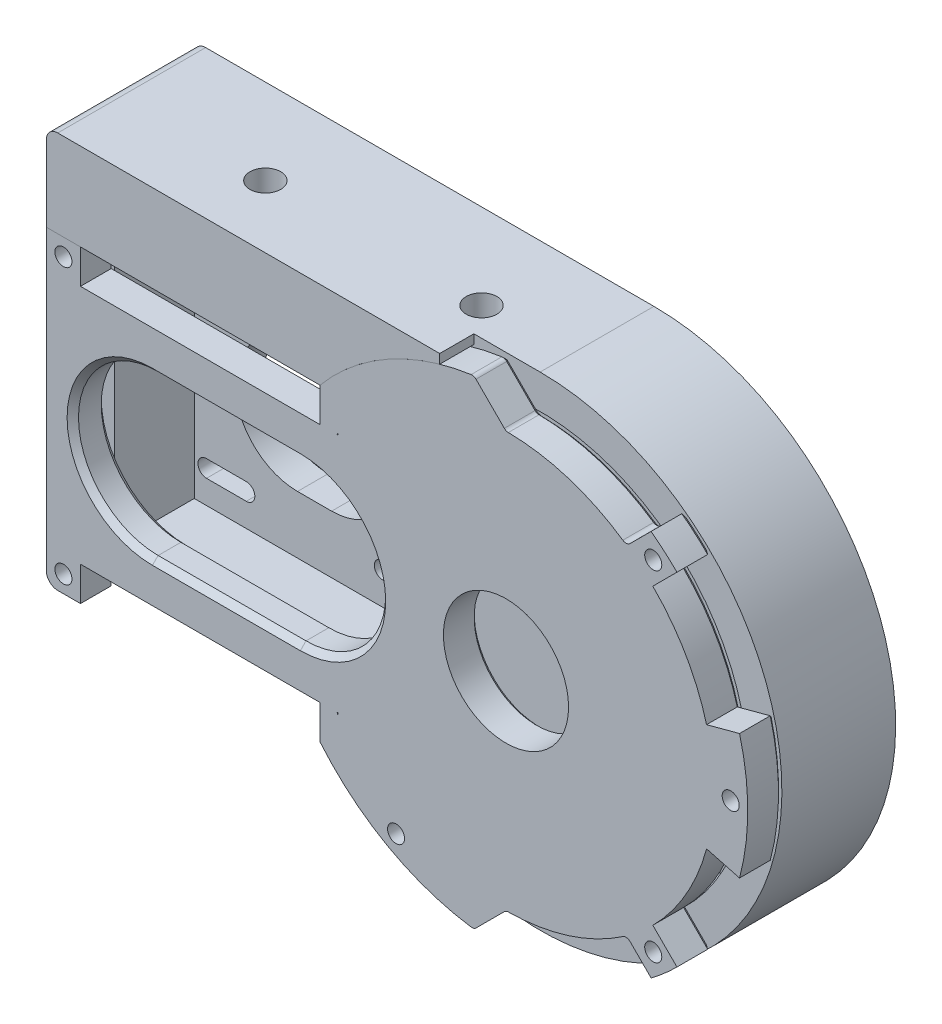
SolidWorks part; units mm, degrees
note: The reader was unsure of these and kept them because the rebuilt part matched: shared geometry of "Sketch3<3>", "Sketch1<3>".
other "Vista explosionada1" [suppressed]
other "Paso de explosión1" [suppressed]
other "Línea de explosión1"
other "Paso de explosión2" [suppressed]
other "Línea de explosión1"
ref_plane "Front Plane" through (0, 0, 0) normal (0, 0, 1) x (1, 0, 0)
ref_plane "Top Plane" through (0, 0, 0) normal (0, 1, 0) x (1, 0, 0)
ref_plane "Right Plane" through (0, 0, 0) normal (1, 0, 0) x (0, 0, -1)
sketch "Sketch1" plane through (0, 0, 0) normal (0, 0, 1) x (1, 0, 0)
  line L0 (21.15, 27.15) -> (-27.15, 27.15)
  line L1 (21.15, -21.15) -> (-21.15, -21.15)
  line L2 (21.15, -21.15) -> (21.15, 21.15)
  line L3 (21.15, 21.15) -> (-21.15, 21.15)
  line L4 (-21.15, -21.15) -> (-21.15, 21.15)
  line L5 (21.15, -21.15) -> (-21.15, 21.15) construction
  line L6 (21.15, 21.15) -> (-21.15, -21.15) construction
  line L7 (21.15, 21.15) -> (71.15, 21.15)
  line L8 (21.15, 21.15) -> (21.15, -21.15)
  line L9 (21.15, -21.15) -> (71.15, -21.15)
  line L10 (71.15, 21.15) -> (71.15, -21.15)
  line L11 (-27.15, -27.15) -> (-27.15, 27.15)
  line L12 (21.15, -27.15) -> (-27.15, -27.15)
  line L13 (21.15, 27.15) -> (24.15, 27.15)
  line L14 (24.15, 27.15) -> (24.15, 21.15)
  line L15 (21.15, -27.15) -> (24.15, -27.15)
  line L16 (24.15, -27.15) -> (24.15, -21.15)
  line L17 (21.15, 33.15) -> (-33.15, 33.15)
  line L18 (-33.15, -33.15) -> (-33.15, 33.15)
  line L19 (21.15, -33.15) -> (-33.15, -33.15)
  circle A0 centre (-15.5, 15.5) radius 1.5
  circle A1 centre (15.5, 15.5) radius 1.5
  circle A2 centre (15.5, -15.5) radius 1.5
  circle A3 centre (-15.5, -15.5) radius 1.5
  circle A4 centre (0, 0) radius 11
  circle A5 centre (0, 0) radius 2.5
  circle A6 centre (53.65, 0) radius 11
  point P0 (0, 0)
  dimension "D2" = 3
  dimension "D3" = 22
  dimension "D4" = 5
  dimension "D6" = 22
  dimension "D1" = 42.3
  dimension "D5" = 31
  dimension "D7" = 53.65
  dimension "D8" = 50
  dimension "D10" = 3
  dimension "D9" = 6
  dimension "D11" = 12
extrude "Boss-Extrude1" add sketch "Sketch1" along normal blind 6 contours L4 L1 L2 L3 A4 A3 A2 A1 A0 | L10 L7 L2 L9 A6
sketch "Sketch3" plane through (0, 0, 0) normal (0, 0, 1) x (1, 0, 0)
  line L0 (16.7864, 21.15) -> (23.9023, 21.15)
  line L1 (71.15, 21.15) -> (-21.15, 21.15) construction
  line L2 (16.7864, -21.15) -> (23.9023, -21.15)
  line L3 (71.15, -21.15) -> (-21.15, -21.15) construction
  circle A1 centre (53.65, 0) radius 36.5
  circle A2 centre (53.65, 0) radius 42.5
  circle A3 centre (53.65, 0) radius 11
  dimension "D1" = 73
  dimension "D3" = 22
  dimension "D2" = 6
extrude "Boss-Extrude2" add sketch "Sketch3" along normal up to surface (6 mm away) contours A1
extrude "Boss-Extrude3" add sketch "Sketch3<3>" along normal blind 20 contours L2 A2 L0 A1
sketch "Sketch3<3>" plane through (0, 0, 0) normal (0, 0, 1) x (1, 0, 0) same geometry as "Sketch3"
extrude "Boss-Extrude4" add sketch "Sketch1<3>" along normal up to surface (20 mm away) contours L15 L16 L9 L1 L4 L3 L7 L14 L13 L0 L11 L12 up to face at (56.7472, 0, 20)
sketch "Sketch1<3>" plane through (0, 0, 0) normal (0, 0, 1) x (1, 0, 0) same geometry as "Sketch1"
sketch "Sketch4" plane through (0, 0, 6) normal (0, 0, 1) x (1, 0, 0)
  line L0 (-19, 15.5) -> (-12, 15.5) construction
  line L1 (-19, 17) -> (-12, 17)
  line L2 (-19, 14) -> (-12, 14)
  line L3 (12, 15.5) -> (19, 15.5) construction
  line L4 (12, 17) -> (19, 17)
  line L5 (12, 14) -> (19, 14)
  line L6 (12, -15.5) -> (19, -15.5) construction
  line L7 (12, -14) -> (19, -14)
  line L8 (12, -17) -> (19, -17)
  line L9 (-12, -15.5) -> (-19, -15.5) construction
  line L10 (-12, -17) -> (-19, -17)
  line L11 (-12, -14) -> (-19, -14)
  line L12 (-3, 0) -> (3, 0) construction
  line L13 (-3, 11) -> (3, 11)
  line L14 (-3, -11) -> (3, -11)
  arc A0 (-19, 17) -> (-19, 14) centre (-19, 15.5) ccw
  arc A1 (-12, 14) -> (-12, 17) centre (-12, 15.5) ccw
  arc A2 (12, 17) -> (12, 14) centre (12, 15.5) ccw
  arc A3 (19, 14) -> (19, 17) centre (19, 15.5) ccw
  arc A4 (12, -14) -> (12, -17) centre (12, -15.5) ccw
  arc A5 (19, -17) -> (19, -14) centre (19, -15.5) ccw
  arc A6 (-12, -17) -> (-12, -14) centre (-12, -15.5) ccw
  arc A7 (-19, -14) -> (-19, -17) centre (-19, -15.5) ccw
  circle A8 centre (-15.5, -15.5) radius 1.5 construction
  circle A9 centre (-15.5, 15.5) radius 1.5 construction
  circle A10 centre (15.5, 15.5) radius 1.5 construction
  circle A11 centre (15.5, -15.5) radius 1.5 construction
  arc A12 (-3, 11) -> (-3, -11) centre (-3, 0) ccw
  arc A13 (3, -11) -> (3, 11) centre (3, 0) ccw
  point P2 (-15.5, 15.5)
  point P7 (15.5, 15.5)
  point P14 (15.5, -15.5)
  point P21 (-15.5, -15.5)
  point P28 (0, 0)
  dimension "D2" = 1.5
  dimension "D4" = 28
  dimension "D1" = 7
  dimension "D3" = 22
extrude "Cut-Extrude1" cut sketch "Sketch4" against normal through all
sketch "Sketch5" plane through (0, 0, 20) normal (0, 0, 1) x (1, 0, 0)
  line L0 (-27.15, -27.15) -> (20.9525, -27.15) construction
  line L1 (-27.15, -27.15) -> (-27.15, 27.15) construction
  line L2 (-27.15, 27.15) -> (20.9525, 27.15) construction
  line L3 (-27.15, -27.15) -> (20.9525, -27.15)
  line L4 (-27.15, -27.15) -> (-27.15, 27.15)
  line L5 (-27.15, 27.15) -> (20.9525, 27.15)
  line L6 (-21.15, -21.15) -> (-21.15, 21.15) construction
  line L8 (-21.15, -21.15) -> (24.15, -21.15) construction
  line L9 (-21.15, -21.15) -> (-21.15, 21.15)
  line L10 (23.9023, -21.15) -> (-21.15, -21.15)
  line L11 (-21.15, 21.15) -> (23.9023, 21.15)
  line L12 (53.65, 0) -> (83.702, 30.052)
  line L13 (-21.15, -21.15) -> (20.9525, -21.15)
  line L14 (-21.15, -21.15) -> (-21.15, -27.15)
  line L15 (-21.15, -27.15) -> (20.9525, -27.15)
  line L16 (20.9525, -21.15) -> (20.9525, -27.15)
  line L17 (-21.15, 21.15) -> (20.9525, 21.15)
  line L18 (-21.15, 21.15) -> (-21.15, 27.15)
  line L19 (-21.15, 27.15) -> (20.9525, 27.15)
  line L20 (20.9525, 21.15) -> (20.9525, 27.15)
  line L21 (53.65, 0) -> (83.702, -30.052)
  line L22 (53.65, 0) -> (116.9274, 0) construction
  line L23 (45.1647, 0) -> (79.4594, -34.2947)
  line L24 (45.1647, 0) -> (79.4594, 34.2947)
  line L25 (53.65, 42.5) -> (53.65, -42.5)
  line L26 (53.65, 0) -> (94.7018, 10.9998)
  line L27 (53.65, 0) -> (94.7018, -10.9998)
  line L28 (24.15, 21.15) -> (-21.15, 21.15) construction
  arc A0 (20.9525, -27.15) -> (20.9525, 27.15) centre (53.65, 0) ccw construction
  arc A1 (20.9525, -27.15) -> (20.9525, 27.15) centre (53.65, 0) ccw
  arc A4 (24.15, -21.4942) -> (24.15, 21.4942) centre (53.65, 0) ccw construction
  arc A5 (23.9023, -21.15) -> (23.9023, 21.15) centre (53.65, 0) ccw
  circle A7 centre (53.65, 0) radius 11 construction
  circle A8 centre (53.65, 0) radius 11
  point P14 (32.6573, 20.0077)
  point P26 (0, 0)
  point P28 (33.8, 21.15)
  point P30 (28.1046, -26.0707)
  point P32 (33.8, 21.15)
  point P34 (25.4157, -23.1317)
  point P35 (23.8668, -21.15)
  point P38 (23.9023, 21.15)
  line M5 (-21.15, -21.15) -> (-21.15, 21.15)
  line M6 (-21.15, 21.15) -> (24.15, 21.15)
  arc M7 (24.15, 21.4942) -> (24.15, -21.4942) centre (53.65, 0) cw
  line M8 (24.15, -21.15) -> (-21.15, -21.15)
  arc M9 (20.9525, -27.15) -> (20.9525, 27.15) centre (53.65, 0) ccw
  line M11 (-27.15, 27.15) -> (-27.15, -27.15)
  line M12 (-27.15, -27.15) -> (20.9525, -27.15)
  line M38 (24.15, 21.15) -> (24.15, 21.4942)
  line M39 (24.15, -21.4942) -> (24.15, -21.15)
  dimension "D4" = 45.0523
  dimension "D1" = 90
  dimension "D3" = 30
  dimension "D2" = 6
extrude "Boss-Extrude6" add sketch "Sketch5" along normal blind 6 separate body contours L18 L5 L14 M5 M11 M12 | A8 L25 L11 L10 M7 M38 M6 M5 M8 M39 | A5 L25 L20 L11 M7 M9 | A5 L16 L25 M8 M9 M7 | A8 L21 L27 M7 | A8 L23 L21 M7 | A8 L25 L23 M7 | A8 L26 L12 M7 | A8 L12 L24 M7 | A8 L24 L25 M7 | L22 A8 L27 A5 | A8 L22 L26 M7 | L24 L12 M7 M9 | L23 L21 M7 M9 | L22 A5 L27 M9 | L22 A1 L26 M7
chamfer "Chamfer2" distance 0.6 angle 45 21 edges at (-20.5, 15.5, 0) (-15.5, 17, 0) (-10.5, 15.5, 0) (-15.5, 14, 0) (-20.5, -15.5, 0) (-15.5, -17, 0) (-10.5, -15.5, 0) (-15.5, -14, 0) (10.5, 15.5, 0) (15.5, 17, 0) (20.5, 15.5, 0) (15.5, 14, 0) (15.5, -17, 0) (20.5, -15.5, 0) (10.5, -15.5, 0) (15.5, -14, 0) (0, 11, 0) (-14, 0, 0) (0, -11, 0) (14, 0, 0) (64.65, 0, 0)
chamfer "Chamfer3" distance 6 angle 45 1 edges at (53.65, 42.5, 23)
fillet "Fillet5" radius 1 6 edges at (48.024, 42.126, 23) (48.024, -42.126, 23) (74.8657, -29.7009, 23) (53.65, -36.5, 23) (53.65, 36.5, 23) (74.8657, 29.7009, 23)
chamfer "Chamfer4" distance 0.6 angle 45 39 edges at (64.5887, 34.8223, 20) (77.3081, 32.1434, 20) (32.857, 37.0662, 20) (50.8678, 39.2822, 20) (77.3081, -32.1434, 20) (64.5887, -34.8223, 20) (50.8678, -39.2822, 20) (47.984, -42.0159, 20) (47.984, 42.0159, 20) (74.8444, 30.0046, 20) (53.6787, 36.5759, 20) (74.8444, -30.0046, 20) (53.6787, -36.5759, 20) (24.15, -21.3221, 20) (24.0261, -21.15, 20) (24.0256, -21.3225, 20) (24.0261, 21.15, 20) (24.15, 21.3221, 20) (24.0256, 21.3225, 20) (64.65, 0, 20) (91.8041, -10.2234, 20) (85.2599, -18.25, 20) (81.5807, -27.9307, 20) (81.5, -32.1033, 20) (32.857, -37.0662, 20) (20.9525, -24.15, 20) (-0.0988, -21.15, 20) (-21.15, -24.15, 20) (-24.15, -27.15, 20) (-27.15, 0, 20) (-24.15, 27.15, 20) (-21.15, 24.15, 20) (-0.0988, 21.15, 20) (20.9525, 24.15, 20) (81.5, 32.1033, 20) (81.5807, 27.9307, 20) (85.2599, 18.25, 20) (91.8041, 10.2234, 20) (96.15, 0, 20)
sketch "Sketch15" plane through (0, 0, 26) normal (0, 0, 1) x (1, 0, 0)
  line L0 (-8.5, 0) -> (17.5, 0) construction
  line L1 (-8.5, 14) -> (17.5, 14)
  line L2 (-8.5, -14) -> (17.5, -14)
  arc A0 (-8.5, 14) -> (-8.5, -14) centre (-8.5, 0) ccw
  arc A1 (17.5, -14) -> (17.5, 14) centre (17.5, 0) ccw
  point P3 (4.5, 0)
  dimension "D2" = 14
  dimension "D1" = 26
  dimension "D3" = 4.5
extrude "Cut-Extrude7" cut sketch "Sketch15" against normal up to next (6 mm away)
chamfer "Chamfer5" distance 1 angle 45 8 edges at (4.5, -14, 20) (4.5, -14, 26) (-22.5, 0, 20) (-22.5, 0, 26) (31.5, 0, 20) (31.5, 0, 26) (4.5, 14, 20) (4.5, 14, 26)
sketch "Sketch17" plane through (0, 0, 0) normal (0, 0, -1) x (-1, 0, 0)
  line L0 (27.15, 27.15) -> (-20.9525, 27.15) construction
  line L1 (27.15, 27.15) -> (-20.9525, 27.15)
  line L2 (27.15, 27.15) -> (27.15, 42.5)
  line L3 (27.15, 42.5) -> (-53.65, 42.5)
  arc A0 (-20.9525, 27.15) -> (-20.9525, -27.15) centre (-53.65, 0) ccw construction
  arc A1 (-20.9525, 27.15) -> (-53.65, 42.5) centre (-53.65, 0) ccw
extrude "Boss-Extrude14" add sketch "Sketch17" against normal up to surface (26 mm away)
sketch "Sketch18" plane through (0, 0, 26) normal (0, 0, 1) x (1, 0, 0)
  line L0 (42, 40.8721) -> (42, 42.5)
  line L1 (-27.15, 42.5) -> (53.65, 42.5) construction
  line L5 (-27.15, 42.5) -> (-27.15, 27.15)
  line L6 (-27.15, 27.15) -> (20.9525, 27.15)
  line L7 (53.65, 42.5) -> (-27.15, 42.5)
  line L8 (-27.15, 42.5) -> (-27.15, 27.15)
  line L9 (-27.15, 27.15) -> (20.9525, 27.15)
  line L10 (53.65, 42.5) -> (-27.15, 42.5)
  arc A1 (53.65, 42.5) -> (20.9525, 27.15) centre (53.65, 0) ccw construction
  arc A2 (53.65, 42.5) -> (20.9525, 27.15) centre (53.65, 0) ccw
  arc A3 (53.65, 42.5) -> (20.9525, 27.15) centre (53.65, 0) ccw
  arc M8 (20.9525, 27.15) -> (53.65, 42.5) centre (53.65, 0) cw
  line M9 (53.65, 42.5) -> (-27.15, 42.5)
  dimension "D2" = 42
  dimension "D1" = 0
extrude "Cut-Extrude8" cut sketch "Sketch18" against normal up to surface (6 mm away) contours L0 M8 M9 up to face at (20.05, 0, 20)
sketch "Sketch19" plane through (0, 21.15, 0) normal (0, -1, 0) x (1, 0, 0)
  line L0 (-27.15, 20) -> (-27.15, 0) construction
  line L1 (3.1213, 19.8) -> (-2.4213, 19.8)
  line L2 (-2.4213, 19.8) -> (-5.1926, 15)
  line L3 (-5.1926, 15) -> (-2.4213, 10.2)
  line L4 (-2.4213, 10.2) -> (3.1213, 10.2)
  line L5 (3.1213, 10.2) -> (5.8926, 15)
  line L6 (5.8926, 15) -> (3.1213, 19.8)
  line L7 (41.1213, 19.8) -> (35.5787, 19.8)
  line L8 (35.5787, 19.8) -> (32.8074, 15)
  line L9 (32.8074, 15) -> (35.5787, 10.2)
  line L10 (35.5787, 10.2) -> (41.1213, 10.2)
  line L11 (41.1213, 10.2) -> (43.8926, 15)
  line L12 (43.8926, 15) -> (41.1213, 19.8)
  circle A0 centre (0.35, 15) radius 4.8 construction
  circle A1 centre (38.35, 15) radius 4.8 construction
  dimension "D1" = 9.6
  dimension "D2" = 27.5
  dimension "D3" = 38
  dimension "D4" = 15
extrude "Cut-Extrude9" cut sketch "Sketch19" against normal blind 15.5
sketch "Sketch20" plane through (0, 21.15, 0) normal (0, -1, 0) x (1, 0, 0)
  circle A0 centre (0.35, 15) radius 2.7
  circle A1 centre (38.35, 15) radius 2.7
  dimension "D2" = 5.4
extrude "Cut-Extrude10" cut sketch "Sketch20" against normal through all
fillet "Fillet8" radius 2 3 edges at (-27.15, 42.5, 13) (-27.15, -27.15, 10) (20.9525, -27.15, 10)
fillet "Fillet9" radius 2 1 edges at (-27.15, -27.15, 23.3)
sketch "Croquis1" plane through (0, 0, 26) normal (0, 0, 1) x (1, 0, 0)
  line L0 (0, 0) -> (-0.0988, 21.15)
  line L1 (-21.15, 21.15) -> (20.9525, 21.15) construction
  line L2 (-0.0988, 21.15) -> (-21.15, 21.15)
  line L3 (-21.15, 21.15) -> (-21.15, 24.15)
  line L4 (-21.15, 21.15) -> (-21.15, 27.15) construction
  line L5 (-21.15, 24.15) -> (-24.15, 24.15)
  line L6 (0, 0) -> (-0.0988, -21.15)
  line L7 (20.9525, -21.15) -> (-21.15, -21.15) construction
  line L8 (-0.0988, -21.15) -> (-21.15, -21.15)
  line L9 (-21.15, -21.15) -> (-21.15, -24.15)
  line L10 (-21.15, -27.15) -> (-21.15, -21.15) construction
  line L11 (-21.15, -24.15) -> (-24.15, -24.15)
  line L18 (53.65, 0) -> (93.15, 0)
  line L19 (53.65, 0) -> (34.3248, 34.4497)
  line L20 (53.65, 0) -> (79.5342, 29.8372)
  line L21 (53.65, 0) -> (79.5342, -29.8372)
  line L22 (53.65, 0) -> (34.3248, -34.4497)
  line L23 (53.65, 0) -> (93.15, 0)
  circle A0 centre (79.5342, 29.8372) radius 1.5
  circle A1 centre (93.15, 0) radius 1.5
  circle A2 centre (79.5342, -29.8372) radius 1.5
  circle A3 centre (34.3248, -34.4497) radius 1.5
  circle A5 centre (53.65, 0) radius 39.5
  circle A6 centre (-24.15, 24.15) radius 1.5
  circle A7 centre (-24.15, -24.15) radius 1.5
  circle A8 centre (34.3248, 34.4497) radius 1.5
  dimension "D1" = 3
  dimension "3" = 3
extrude "Cortar-Extruir1" cut sketch "Croquis1" against normal blind 10
move or copy body "Sólido-Mover/Copiar1" [suppressed] bodies to move or copy 125 copy no translate (0, 0, 24.581) parameters "D1"=0, "D2"=0, "D3"=0
move or copy body "Sólido-Mover/Copiar2" [suppressed] bodies to move or copy 129 copy no translate (0, 0, -31.2597) parameters "D1"=0, "D2"=0, "D3"=0
